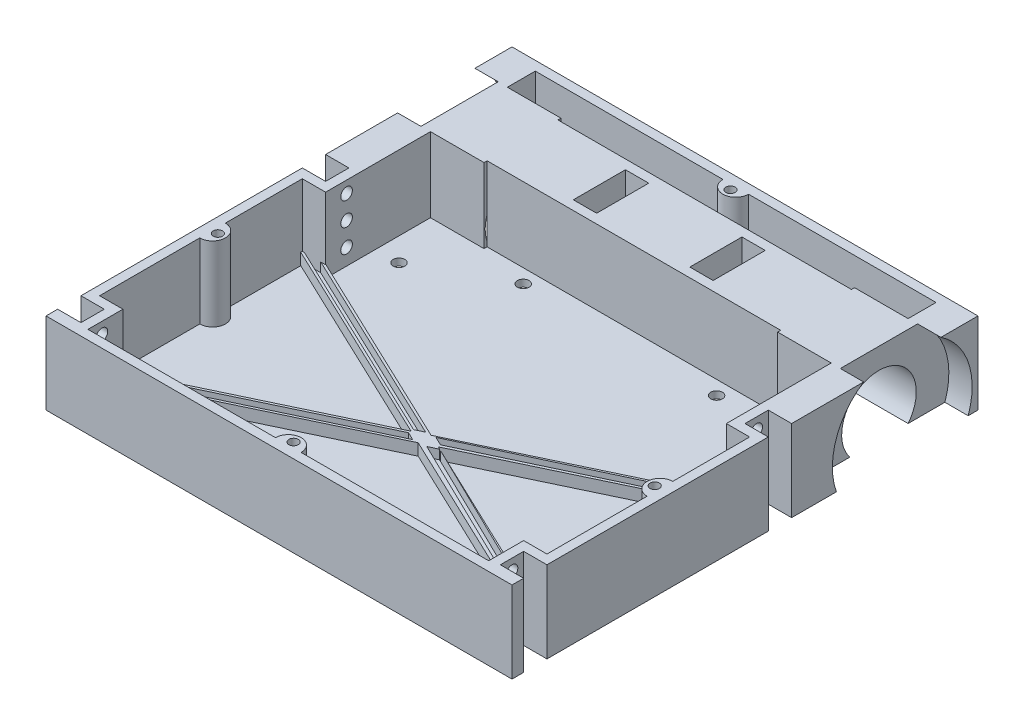
SolidWorks part; units mm, degrees
ref_plane "Plan de face" through (0, 0, 0) normal (0, 0, 1) x (1, 0, 0)
ref_plane "Plan de dessus" through (0, 0, 0) normal (0, 1, 0) x (1, 0, 0)
ref_plane "Plan de droite" through (0, 0, 0) normal (1, 0, 0) x (0, 0, -1)
sketch "Esquisse2" plane through (0, 0, 0) normal (0, 1, 0) x (1, 0, 0)
  line L1 (100, 100) -> (-100, 100)
  line L2 (100, 100) -> (100, -100)
  line L3 (100, -100) -> (-100, -100)
  line L4 (-100, 100) -> (-100, -100)
  line L5 (100, 100) -> (-100, -100) construction
  line L6 (100, -100) -> (-100, 100) construction
  point P0 (0, 0)
  dimension "D1" = 200
  dimension "D2" = 200
extrude "BASE" add sketch "Esquisse2" along normal blind 35
sketch "Esquisse3" plane through (100, 0, 0) normal (1, 0, 0) x (0, 0, -1)
  line L0 (100, 10) -> (31.0775, 10) construction
  line L1 (100, 35) -> (100, 0) construction
  line L2 (-100, 0) -> (100, 0) construction
  circle A0 centre (67.5, 10) radius 15
  point P4 (67.5, 10)
  dimension "D3" = 30
  dimension "D1" = 32.5
  dimension "D2" = 10
extrude "BLOC MOTEUR 1." cut sketch "Esquisse3" against normal blind 80
sketch "Esquisse4" plane through (0, 0, 0) normal (0, -1, 0) x (1, 0, 0)
  line L0 (20, -78.6803) -> (100, -78.6803) construction
  line L1 (20, -56.3197) -> (30, -56.3197)
  line L2 (20, -56.3197) -> (20, -78.6803)
  line L3 (20, -78.6803) -> (30, -78.6803)
  line L4 (30, -56.3197) -> (30, -78.6803)
  dimension "D1" = 10
extrude "ACCES MOTEUR" cut sketch "Esquisse4" against normal blind 37
ref_plane "PLAN SYM " through (0, 0, 0) normal (1, 0, 0) x (0, 0, -1)
sketch "Esquisse6" plane through (100, 0, 0) normal (1, 0, 0) x (0, 0, -1)
  line L0 (52.5, 10) -> (82.5, 10) construction
  arc A0 (56.3197, 20) -> (56.3197, 0) centre (67.5, 10) ccw construction
  arc A1 (78.6803, 0) -> (56.3197, 0) centre (67.5, 10) ccw construction
  circle A2 centre (67.5, 10) radius 16.01
  dimension "D1" = 32.02
extrude "BLOC MOTEUR 2" cut sketch "Esquisse6" against normal blind 37
mirror "SYM BLOC MOTEUR" about plane through (0, 0, 0) normal (1, 0, 0) of "ACCES MOTEUR", "BLOC MOTEUR 1.", "BLOC MOTEUR 2"
sketch "Esquisse7" plane through (0, 0, 0) normal (0, -1, 0) x (1, 0, 0)
  line L0 (-76, -90.0028) -> (-76, -27.4971) construction
  line L1 (-100, -54.9972) -> (-63, -54.9972) construction
  line L2 (-41.5, -56.3197) -> (-41.5, -67.469) construction
  line L3 (-63, -56.3197) -> (-20, -56.3197) construction
  line L4 (-63, -80.0028) -> (-100, -80.0028) construction
  line L5 (-20, -78.6803) -> (-63, -78.6803) construction
  line L7 (-41.5, -88.6803) -> (-41.5, -20.9291) construction
  circle A0 centre (-76, -27.4971) radius 2.5
  circle A1 centre (-41.5, -46.3197) radius 2.5
  circle A2 centre (-41.5, -88.6803) radius 2.5
  circle A3 centre (-76, -90.0028) radius 2.5
  point P8 (-64, -44.9972)
  point P9 (-76, -90.0028)
  point P10 (-41.5, -88.6803)
  point P11 (-41.5, -46.3197)
  dimension "D5" = 5
  dimension "D6" = 5
  dimension "D7" = 5
  dimension "D8" = 5
  dimension "D1" = 10
  dimension "D2" = 10
  dimension "D3" = 10
  dimension "D4" = 10
  dimension "D9" = 13
extrude "VIS MOTEUR" cut sketch "Esquisse7" against normal through all
mirror "SYM VIS" about plane through (0, 0, 0) normal (1, 0, 0) of "VIS MOTEUR"
sketch "Esquisse8" plane through (0, 0, 0) normal (0, -1, 0) x (1, 0, 0)
  line L0 (-100, 100) -> (100, 100) construction
  line L1 (-100, -54.9972) -> (-100, 100) construction
  line L2 (100, 100) -> (100, -54.9972) construction
  circle A0 centre (-55, 77.5) radius 2.5
  circle A1 centre (55, 77.5) radius 2.5
  point P0 (-55, 77.5)
  point P1 (55, 77.5)
  dimension "D5" = 5
  dimension "D6" = 5
  dimension "D1" = 22.5
  dimension "D2" = 45
  dimension "D3" = 22.5
  dimension "D4" = 45
extrude "VIS PATIN" cut sketch "Esquisse8" against normal through all
sketch "Esquisse12" plane through (-100, 0, 0) normal (-1, 0, 0) x (0, 0, 1)
  circle A0 centre (-67.5, 10) radius 30
  dimension "D1" = 60
extrude "ESPACE ROUE " cut sketch "Esquisse12" against normal blind 10
mirror "SYM ESPACE ROUE" about plane through (0, 0, 0) normal (1, 0, 0) of "ESPACE ROUE "
sketch "Esquisse23" plane through (100, 0, 0) normal (1, 0, 0) x (0, 0, -1)
  line L0 (37.5184, 11.0504) -> (37.5184, -3.5531) construction
  line L1 (-95, 35) -> (-85, 35)
  line L2 (-95, 35) -> (-95, 0)
  line L3 (-95, 0) -> (-85, 0)
  line L4 (-85, 35) -> (-85, 0)
  line L6 (-100, 0) -> (39.2157, 0) construction
  line L8 (-100, 35) -> (-100, 0) construction
  line L9 (-100, 35) -> (50.9169, 35) construction
  line L10 (20, 0) -> (10, 0)
  line L11 (20, 0) -> (20, 35)
  line L12 (20, 35) -> (10, 35)
  line L13 (10, 0) -> (10, 35)
  arc A1 (50.9169, 35) -> (39.2157, 0) centre (67.5, 10) ccw construction
  point P19 (15, 0)
  dimension "D1" = 5
  dimension "D2" = 10
  dimension "D4" = 10
  dimension "D5" = 115
extrude "VIDE TIGE" cut sketch "Esquisse23" against normal blind 10
mirror "SYM TIGE" about plane through (0, 0, 0) normal (1, 0, 0) of "VIDE TIGE"
sketch "Esquisse25" plane through (90, 0, 0) normal (1, 0, 0) x (0, 0, -1)
  line L0 (-95, 35) -> (-85, 0) construction
  line L1 (-85, 0) -> (-90, 0) construction
  line L2 (-95, 0) -> (-85, 0) construction
  line L3 (-90, 0) -> (-90, 35) construction
  line L4 (-85, 35) -> (-95, 35) construction
  line L5 (10, 35) -> (-85, 0) construction
  line L6 (-85, 0) -> (-85, 35) construction
  line L7 (-85, 35) -> (-37.5, 35) construction
  line L8 (-85, 35) -> (10, 35) construction
  line L9 (-37.5, 35) -> (-37.5, -2.9576) construction
  circle A0 centre (-90, 30) radius 2.5
  circle A1 centre (-90, 20) radius 2.5
  circle A2 centre (-90, 10) radius 2.5
  circle A3 centre (15, 10) radius 2.5
  circle A4 centre (15, 30) radius 2.5
  circle A5 centre (15, 20) radius 2.5
  dimension "D1" = 5
  dimension "D2" = 5
  dimension "D3" = 5
  dimension "D4" = 10
  dimension "D5" = 10
  dimension "D6" = 5
extrude "VIDE VIS" cut sketch "Esquisse25" against normal up to next
ref_plane "PLAN COUPE MILIEU" through (0, 4, 0) normal (0, 1, 0) x (1, 0, 0)
sketch "Esquisse27" plane through (0, 4, 0) normal (0, 1, 0) x (1, 0, 0)
  line L0 (-96, -81) -> (-96, 6)
  line L1 (-96, 6) -> (-86, 6)
  line L2 (-86, 6) -> (-86, 16.1422)
  line L3 (-86, 16.1422) -> (-86, 50.9972)
  line L4 (-86, 50.9972) -> (-63, 50.9972)
  line L5 (-63, 50.9972) -> (-63, 52.3197)
  line L6 (-63, 52.3197) -> (63, 52.3197)
  line L7 (0, -96) -> (0, 96) construction
  line L8 (86, -96) -> (-86, -96)
  line L9 (-86, -96) -> (-86, -81)
  line L10 (-86, -81) -> (-96, -81)
  line L11 (-100, -100) -> (100, -100) construction
  line L12 (-90, -85) -> (-90, -95) construction
  line L13 (-90, -85) -> (-100, -85) construction
  line L14 (-100, 10) -> (-100, -85) construction
  line L15 (-90, 10) -> (-90, 20) construction
  line L16 (-90, 54.9972) -> (-63, 54.9972) construction
  line L17 (-63, 56.3197) -> (-20, 56.3197) construction
  line L18 (-90, 80.0028) -> (-90, 95.7843) construction
  line L19 (-86, 84.0028) -> (-63, 84.0028)
  line L20 (-90, 10) -> (-100, 10) construction
  line L21 (86, 96) -> (-86, 96)
  line L22 (-86, 96) -> (-86, 84.0028)
  line L23 (100, 100) -> (-100, 100) construction
  line L24 (-63, 80.0028) -> (-90, 80.0028) construction
  line L25 (-63, 84.0028) -> (-63, 82.6803)
  line L26 (-63, 82.6803) -> (63, 82.6803)
  line L27 (63, 84.0028) -> (63, 82.6803)
  line L28 (-20, 78.6803) -> (-63, 78.6803) construction
  line L29 (86, 96) -> (86, 84.0028)
  line L30 (86, 84.0028) -> (63, 84.0028)
  line L31 (86, -81) -> (96, -81)
  line L32 (86, -96) -> (86, -81)
  line L33 (63, 50.9972) -> (63, 52.3197)
  line L34 (86, 50.9972) -> (63, 50.9972)
  line L35 (86, 16.1422) -> (86, 50.9972)
  line L36 (86, 6) -> (86, 16.1422)
  line L37 (96, 6) -> (86, 6)
  line L38 (96, -81) -> (96, 6)
  point P14 (-90, -90)
  point P48 (0, 82.6803)
  point P49 (0, 52.3197)
  dimension "D1" = 4
  dimension "D2" = 4
  dimension "D3" = 4
  dimension "D4" = 4
  dimension "D5" = 4
  dimension "D6" = 4
  dimension "D7" = 4
  dimension "D8" = 4
  dimension "D9" = 4
  dimension "D10" = 4
  dimension "D11" = 4
  dimension "D12" = 0
  dimension "D13" = 4
extrude "VIDE BASE" cut sketch "Esquisse27" along normal up to surface (31 mm away) and the other way blind 1 up to face at (-25, 35, -67.5)
sketch "Esquisse29" plane through (0, 4, 0) normal (0, 1, 0) x (1, 0, 0)
  line L0 (-100, -85) -> (100, -85) construction
  line L1 (-48.5364, -57.7871) -> (-52.9831, -59.8993)
  line L2 (100, -85) -> (-100, 10) construction
  line L3 (-100, 10) -> (100, 10) construction
  line L4 (100, 10) -> (-100, -85) construction
  line L5 (-94.1733, 10) -> (0, -34.7323)
  line L6 (100, -85) -> (100, 10) construction
  line L7 (-100, 7.2323) -> (-5.8267, -37.5)
  line L8 (-100, 10) -> (-100, -85) construction
  line L9 (53.7123, -60.2456) -> (58.1589, -62.3578)
  line L10 (0, -37.5) -> (0, -85) construction
  line L11 (94.1733, 10) -> (0, -34.7323)
  line L12 (100, 7.2323) -> (5.8267, -37.5)
  line L13 (0, -40.2677) -> (94.1733, -85)
  line L14 (5.8267, -37.5) -> (53.7123, -60.2456)
  line L15 (-5.8267, -37.5) -> (-48.5364, -57.7871)
  line L16 (0, -40.2677) -> (-94.1733, -85)
  line L17 (-100, -82.2323) -> (-100, -85)
  line L18 (-100, -85) -> (-94.1733, -85)
  line L19 (94.1733, -85) -> (100, -85)
  line L20 (100, -85) -> (100, -82.2323)
  line L21 (94.1733, 10) -> (100, 10)
  line L22 (100, 10) -> (100, 7.2323)
  line L23 (-94.1733, 10) -> (-100, 10)
  line L24 (-100, 10) -> (-100, 7.2323)
  line L25 (-52.9831, -59.8993) -> (-100, -82.2323)
  line L26 (58.1589, -62.3578) -> (100, -82.2323)
  point P4 (0, -37.5)
  dimension "D1" = 2.5
  dimension "D2" = 2.5
extrude "BOSS - CROIX" add sketch "Esquisse29" along normal blind 4 and the other way blind 2.5
sketch "Esquisse30" plane through (0, 35, 0) normal (0, 1, 0) x (1, 0, 0)
  line L0 (0, 0) -> (0, -96.0319) construction
  line L1 (86, -96) -> (-86, -96) construction
  line L2 (-12.2008, 96) -> (10, 96) construction
  line L3 (-5.5, -96) -> (5.5, -96) construction
  line L4 (0, 0) -> (0, 102.788) construction
  line L6 (-86, 96) -> (86, 96) construction
  line L7 (-5.5, 96) -> (5.5, 96) construction
  line L8 (-5.5, 96) -> (5.5, 96)
  line L9 (-5.5, -96) -> (5.5, -96)
  line L10 (-96, 6) -> (-96, -71) construction
  line L13 (-96, -27) -> (-96, -38)
  line L14 (96, -27) -> (96, -38)
  arc A0 (5.5, -96) -> (-5.5, -96) centre (0, -96) ccw
  circle A1 centre (0, -93.75) radius 2
  arc A2 (-5.5, 96) -> (5.5, 96) centre (0, 96) ccw
  circle A3 centre (0, 93.75) radius 2
  arc A4 (-96, -38) -> (-96, -27) centre (-96, -32.5) ccw
  circle A5 centre (-93.75, -32.5) radius 2
  circle A6 centre (93.75, -32.5) radius 2
  arc A7 (96, -38) -> (96, -27) centre (96, -32.5) cw
  point P11 (-5.5, -96)
  point P12 (10, -96)
  dimension "D1" = 11
  dimension "D3" = 4
  dimension "D4" = 11
  dimension "D5" = 4
  dimension "D7" = 11
  dimension "D8" = 4
  dimension "D2" = 2.25
  dimension "D6" = 2.25
  dimension "D9" = 2.25
extrude "BOSS VIS" add sketch "Esquisse30" against normal up to surface (35 mm away) up to face at (55, 0, 75)
sketch "Esquisse31" plane through (0, 0, 0) normal (0, -1, 0) x (1, 0, 0)
  circle A0 centre (0, 93.75) radius 2
  circle A1 centre (-93.75, 32.5) radius 2
  circle A2 centre (0, -93.75) radius 2
  circle A3 centre (93.75, 32.5) radius 2
  dimension "D1" = 4
  dimension "D2" = 4
  dimension "D3" = 4
  dimension "D4" = 4
extrude "VIDE VIS COUVERCLE" cut sketch "Esquisse31" against normal blind 5
sketch "Esquisse36" plane through (0, 4, 0) normal (0, 1, 0) x (1, 0, 0)
  line L0 (-95.075, -81) -> (-5.8267, -38.6071)
  line L1 (-96, -81) -> (-86, -81) construction
  line L2 (-5.8267, -36.3929) -> (-95.075, 6)
  line L3 (-8.1574, -37.5) -> (0, -33.6252) construction
  line L4 (-95.075, 6) -> (-88.0829, 6)
  line L5 (-88.0829, 6) -> (-2.3307, -34.7323)
  line L6 (0, -34.7323) -> (0, -40.2677) construction
  line L7 (-95.075, -81) -> (-88.0829, -81)
  line L8 (-88.0829, -81) -> (-2.3307, -40.2677)
  line L9 (-96, 5.3323) -> (-5.8267, -37.5) construction
  line L10 (-86, 6.1177) -> (0, -34.7323) construction
  line L11 (-5.8267, -37.5) -> (-96, -80.3323) construction
  line L12 (0, -40.2677) -> (-86, -81.1177) construction
  line L13 (-86, 6) -> (-96, 6) construction
  line L14 (-96, -80.3323) -> (-5.8267, -37.5) construction
  line L15 (-86, -81.1177) -> (0, -40.2677) construction
  line L16 (88.0829, -81) -> (3.248, -39.832)
  line L17 (88.0829, 6) -> (1.8204, -34.4899)
  line L18 (5.5733, -36.2725) -> (95.075, 6)
  line L19 (95.075, -81) -> (7.0009, -38.0493)
  line L20 (95.075, -81) -> (88.0829, -81)
  line L21 (95.075, 6) -> (88.0829, 6)
  line L22 (-5.8267, -37.5) -> (0, -34.7323) construction
  line L23 (0, -34.7323) -> (5.8267, -37.5) construction
  line L24 (5.8267, -37.5) -> (0, -40.2677) construction
  line L25 (0, -40.2677) -> (-5.8267, -37.5) construction
  line L26 (-8.1574, -37.5) -> (0, -41.3748) construction
  line L27 (0, -41.3748) -> (8.1574, -37.5) construction
  line L28 (8.1574, -37.5) -> (0, -33.6252) construction
  line L29 (-5.8267, -36.3929) -> (-2.3307, -34.7323)
  line L30 (1.8204, -34.4899) -> (5.5733, -36.2725)
  line L31 (7.0009, -38.0493) -> (3.248, -39.832)
  line L32 (-2.3307, -40.2677) -> (-5.8267, -38.6071)
  dimension "D1" = 1
  dimension "D2" = 1
  dimension "D3" = 1
  dimension "D4" = 1
  dimension "D5" = 1
  dimension "D6" = 1
  dimension "D7" = 1
  dimension "D8" = 1
extrude "VIDE CROIX" cut sketch "Esquisse36" along normal up to surface (4 mm away) up to face at (0, 8, 37.5)
